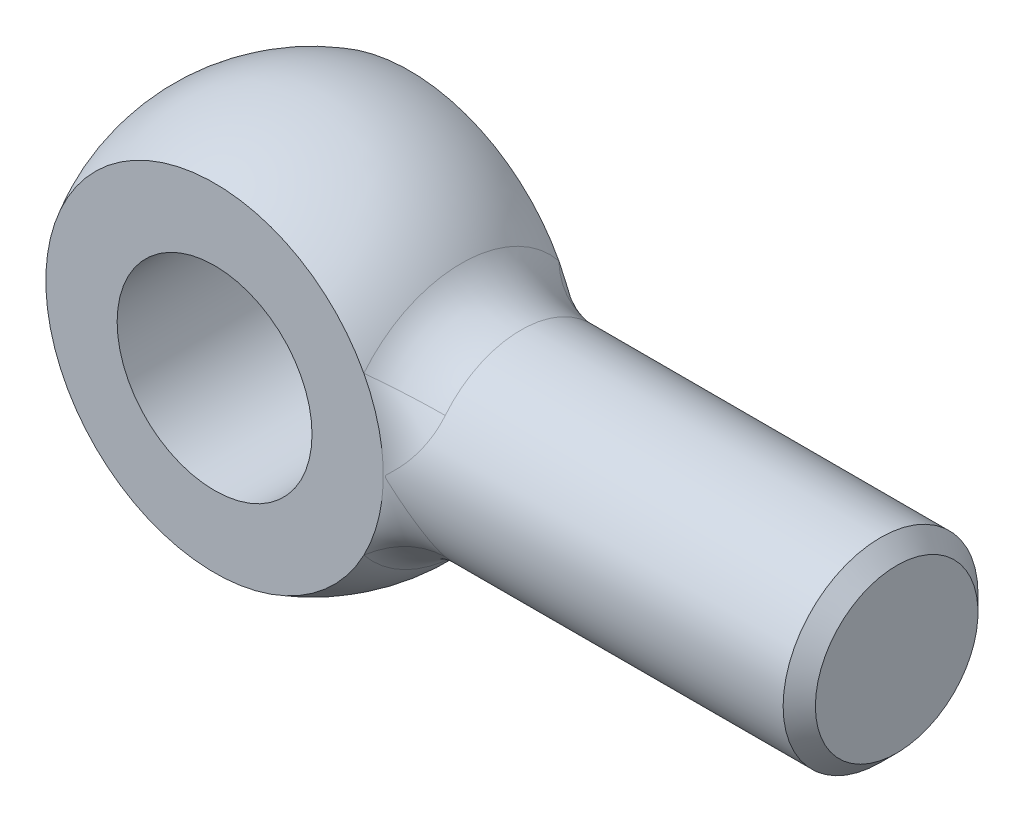
SolidWorks part; units mm, degrees
ref_plane "Plane1" through (0, 0, 0) normal (0, 0, 1) x (1, 0, 0)
ref_plane "Plane2" through (0, 0, 0) normal (0, 1, 0) x (1, 0, 0)
ref_plane "Plane3" through (0, 0, 0) normal (1, 0, 0) x (0, 0, -1)
sketch "BodySke" plane through (0, 0, 0) normal (0, 0, 1) x (1, 0, 0)
  line L0 (0, 0) -> (0, 5)
  line L3 (0, 5) -> (29.172, 5)
  line L4 (30, 4.172) -> (30, 0)
  line L5 (30, 0) -> (0, 0)
  line L6 (-31.75, 0) -> (127, 0) construction
  line L8 (30, 4.172) -> (29.172, 5)
  line L10 (30, -4.172) -> (29.172, -5) construction
  line L11 (1.5, 4.525) -> (1.5, -1.825) construction
  line L12 (0, 5) -> (0, -1.825) construction
  line L13 (10, 4.525) -> (10, -1.825) construction
  dimension "Diameter" = 10
  dimension "Length" = 30
revolve "Base-Revolve" add sketch "BodySke" angle 360 about L6
cosmetic thread "ThreadCosmetic" [suppressed] parameters "Thread_length"=18.5, "Thread_minor"=8.344
sketch "EyeSke" plane through (0, 0, 0) normal (1, 0, 0) x (0, 0, -1)
  line L0 (5.0012, 0) -> (-5.0013, 0)
  line L1 (5.0012, 8.6595) -> (5.0012, 0)
  line L2 (-5.0013, 8.6595) -> (-5.0013, 0)
  line L3 (5.0012, 0) -> (-5.0013, 0) construction
  arc A0 (5.0012, 8.6595) -> (-5.0013, 8.6595) centre (0, 0) ccw
  dimension "Head_dia" = 20
  dimension "Head_thickness" = 10.0025
revolve "Eye" add sketch "EyeSke" angle 360 about L3
sketch "PupilSke" plane through (0, 0, 5.0013) normal (0, 0, 1) x (1, 0, 0)
  circle A0 centre (0, 0) radius 5
  dimension "Diameter" = 10
extrude "Pupil" cut sketch "PupilSke" against normal through all
fillet "Fillet1" radius 4 1 edges at (8.6603, 0, 5)
sketch "ThdSchSke" plane through (0, 0, 0) normal (0, 0, 1) x (1, 0, 0)
  line L0 (11.5, -4.172) -> (10.9202, -5)
  line L1 (11.5, -4.172) -> (12.0798, -5)
  line L2 (12.0798, -5) -> (12.0798, -6.25)
  line L3 (-3.175, 0) -> (5.1513, 0) construction
  line L5 (12.0798, -6.25) -> (10.9202, -6.25)
  line L6 (10.9202, -6.25) -> (10.9202, -5)
  dimension "Diameter" = 10
  dimension "Thread_minor" = 8.344
  dimension "Start" = 11.5
revolve "ThreadSchematic" [suppressed] cut sketch "ThdSchSke" angle 360 about L3
pattern_linear "ThdSchPat" [suppressed]
equation "\"Thread_minor@ThreadCosmetic\"  =  \"Minor_dia@BodySke\""
equation "\"Thread_length@ThreadCosmetic\" = \"Thread_nom@BodySke\" - \"Advance@BodySke\""
equation "\"Thread_minor@ThdSchSke\" = \"Minor_dia@BodySke\""
equation "\"Diameter@ThdSchSke\" = \"Diameter@BodySke\""
equation "\"Overcut@ThdSchSke\" = \"Diameter@BodySke\" * 1.25"
equation "\"Start@ThdSchSke\" = \"Length@BodySke\" - \"Thread_length@ThreadCosmetic\""
equation "\"Num_threads@ThdSchPat\" = int( \"Thread_length@ThreadCosmetic\" / \"Advance@BodySke\" + 0.999 )  + 1"
equation "\"Advance@ThdSchPat\" = \"Thread_length@ThreadCosmetic\" /  (\"Num_threads@ThdSchPat\" - 1) 'relax it"
equation "\"Num_threads@ThdSchPat\" = \"Num_threads@ThdSchPat\" - sgn( \"Num_threads@ThdSchPat\" - 1) '---chamfered tips only---"
